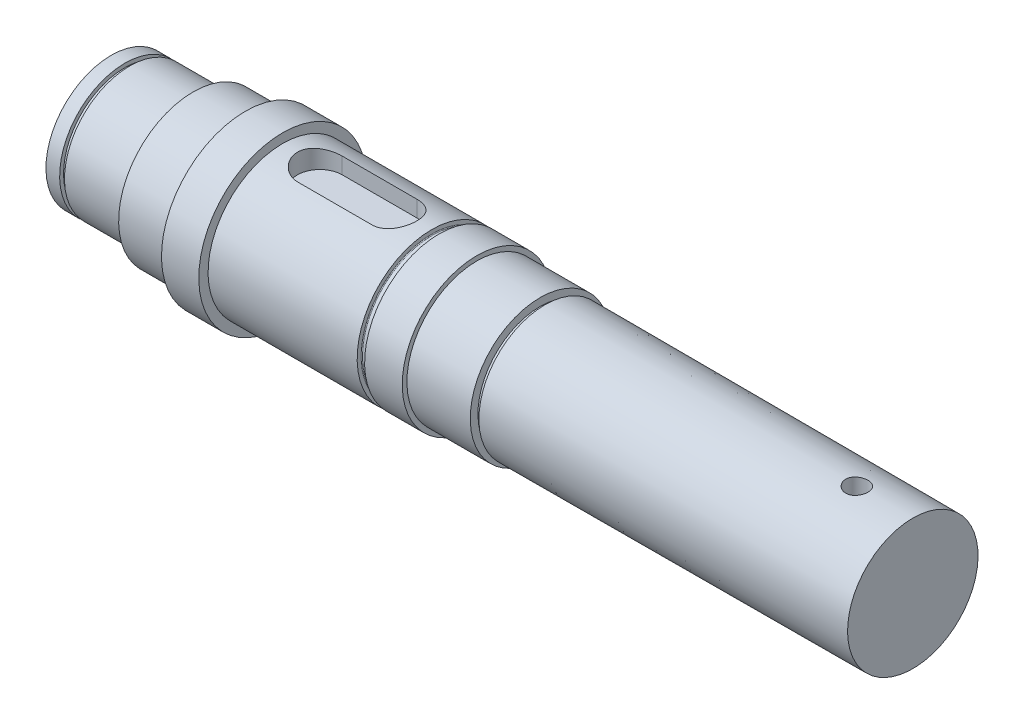
SolidWorks part; units mm, degrees
material "1023 Carbon Steel Sheet (SS)"
ref_plane "Front Plane" through (0, 0, 0) normal (0, 0, 1) x (1, 0, 0)
ref_plane "Top Plane" through (0, 0, 0) normal (0, 1, 0) x (1, 0, 0)
ref_plane "Right Plane" through (0, 0, 0) normal (1, 0, 0) x (0, 0, -1)
sketch "Sketch1" plane through (0, 0, 0) normal (0, 0, 1) x (1, 0, 0)
  line L0 (5.8149, -5.9149) -> (5.8149, 11.5851)
  line L1 (5.8149, 11.5851) -> (9.4831, 11.5851)
  line L2 (27.8149, 11.5851) -> (27.8149, 14.0851)
  line L3 (27.8149, 14.0851) -> (41.8149, 14.0851)
  line L4 (41.8149, 14.0851) -> (41.8149, 16.5851)
  line L5 (41.8149, 16.5851) -> (51.8149, 16.5851)
  line L6 (51.8149, 16.5851) -> (51.8149, 14.0851)
  line L7 (51.8149, 14.0851) -> (91.8149, 14.0851)
  line L8 (91.8149, 14.0851) -> (91.8149, 13.0451)
  line L9 (92.0149, 12.8451) -> (93.6149, 12.8451)
  line L10 (93.8149, 13.0451) -> (93.8149, 14.0851)
  line L11 (93.8149, 14.0851) -> (103.9149, 14.0851)
  line L12 (103.9149, 14.0851) -> (103.9149, 12.8351)
  line L13 (103.9149, 12.8351) -> (120.9149, 12.8351)
  line L14 (5.8149, -5.9149) -> (220.9149, -5.9149)
  line L15 (220.9149, -5.9149) -> (220.9149, 11.5877)
  line L16 (221.9994, -5.9149) -> (1.1932, -5.9149) construction
  line L17 (120.9149, 12.8351) -> (120.9149, 10.7675)
  line L18 (122.2149, 11.8175) -> (220.9149, 11.5877)
  line L19 (10.7831, 11.5851) -> (10.7831, 10.5351)
  line L20 (10.7831, 10.5351) -> (9.4831, 10.5351)
  line L21 (9.4831, 10.5351) -> (9.4831, 11.5851)
  line L22 (10.7831, 11.5851) -> (27.8149, 11.5851)
  line L24 (120.9149, 10.7675) -> (122.2149, 10.7675)
  line L25 (122.2149, 10.7675) -> (122.2149, 11.8175)
  arc A0 (92.0149, 12.8451) -> (91.8149, 13.0451) centre (92.0149, 13.0451) cw
  arc A1 (93.6149, 12.8451) -> (93.8149, 13.0451) centre (93.6149, 13.0451) ccw
  dimension "D7" = 17
  dimension "D5" = 0.2
  dimension "D2" = 40
  dimension "D3" = 1.3
  dimension "D4" = 40
  dimension "D6" = 10
  dimension "D8" = 1.05
  dimension "D9" = 14
  dimension "D10" = 10.1
  dimension "D11" = 1.25
  dimension "D14" = 1.04
  dimension "D12" = 45
  dimension "D13" = 35
  dimension "D15" = 1.6
  dimension "D16" = 22
  dimension "D17" = 1.3
  dimension "D18" = 1.05
  dimension "D19" = 17.5
revolve "Revolve1" add sketch "Sketch1" angle 360 about L16
sketch "Sketch2" plane through (0, 0, 0) normal (0, 1, 0) x (1, 0, 0)
  line L0 (61.8149, 0) -> (81.8149, 0) construction
  line L1 (61.8149, 6) -> (81.8149, 6)
  line L2 (61.8149, -6) -> (81.8149, -6)
  line L7 (91.8149, -20) -> (91.8149, 20) construction
  arc A0 (61.8149, 6) -> (61.8149, -6) centre (61.8149, 0) ccw
  arc A1 (81.8149, -6) -> (81.8149, 6) centre (81.8149, 0) ccw
  point P3 (71.8149, 0)
  point P8 (87.8149, 0)
  point P9 (55.8149, 0)
  dimension "D3" = 4
  dimension "D1" = 12
  dimension "D2" = 32
extrude "Cut-Extrude1" cut sketch "Sketch2" against normal blind 6.2 from offset 15
sketch "Sketch3" plane through (0, 0, 0) normal (0, 1, 0) x (1, 0, 0)
  line L1 (220.9149, -17.5026) -> (220.9149, 17.5026) construction
  circle A0 centre (205.9149, 0) radius 3
  dimension "D1" = 15
extrude "Cut-Extrude2" cut sketch "Sketch3" against normal mid plane 50
ref_axis "Axis1" through (5.8149, -25.1649, 0) along (0, 1, 0)
